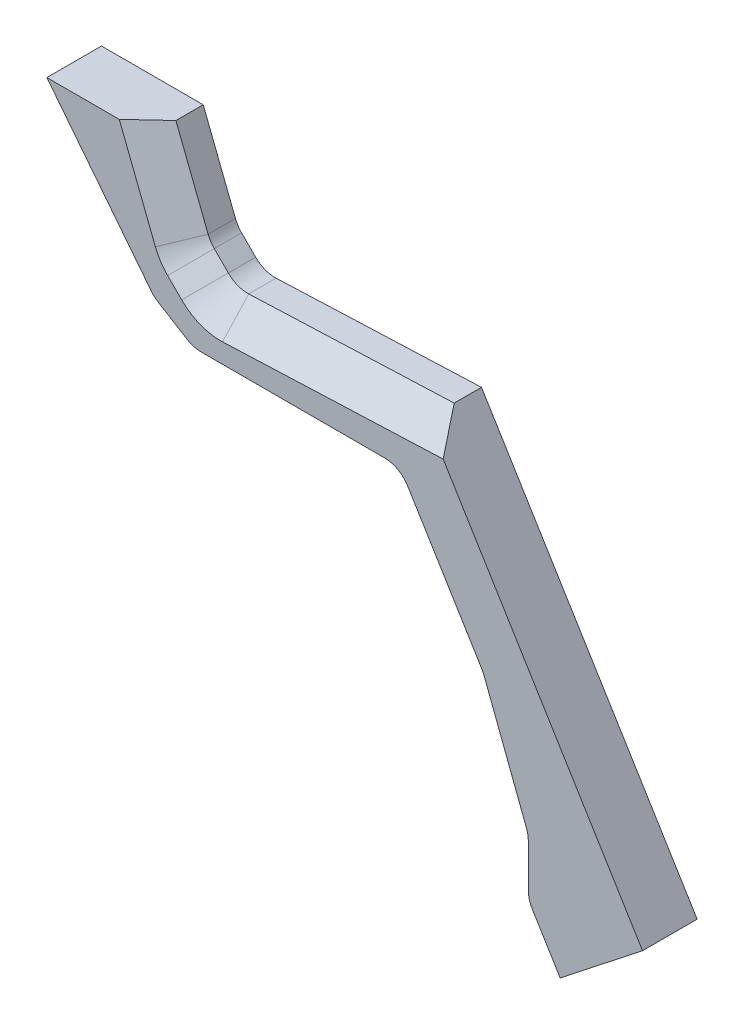
SolidWorks part; units mm, degrees
ref_plane "Front Plane" through (0, 0, 0) normal (0, 0, 1) x (1, 0, 0)
ref_plane "Top Plane" through (0, 0, 0) normal (0, 1, 0) x (1, 0, 0)
ref_plane "Right Plane" through (0, 0, 0) normal (1, 0, 0) x (0, 0, -1)
sketch "Sketch1" plane through (0, 0, 0) normal (0, 0, 1) x (1, 0, 0)
  line L0 (536.696, 136.2549) -> (560.9431, 105.4362)
  line L1 (536.696, 136.2549) -> (607.9061, 136.2549) construction
  line L2 (572.5936, 98.9345) -> (615.1948, 98.9345)
  line L3 (620.6127, 95.8964) -> (637.801, 67.7789)
  line L4 (638.3138, 66.7361) -> (648.2078, 40.8769)
  line L5 (648.6271, 38.6077) -> (648.6271, 28.5432)
  line L6 (649.5592, 25.2312) -> (652.3824, 20.6128)
  line L7 (652.3824, 20.6128) -> (656.0389, 14.6314)
  line L8 (656.0389, 14.6314) -> (675.1811, 29.6919)
  line L9 (675.1811, 29.6919) -> (625.0443, 111.7085)
  line L10 (625.0443, 111.7085) -> (577.2803, 109.8048)
  line L11 (567.8459, 117.1036) -> (560.3494, 136.2549)
  line L12 (536.696, 136.2549) -> (560.3494, 136.2549)
  line L13 (562.6176, 103.9472) -> (569.2776, 99.8691)
  line L14 (569.2689, 114.9281) -> (572.5373, 111.6597)
  arc A0 (648.6271, 28.5432) -> (649.5592, 25.2312) centre (654.9771, 28.5432) ccw
  arc A1 (615.1948, 98.9345) -> (620.6127, 95.8964) centre (615.1948, 92.5845) cw
  arc A2 (637.801, 67.7789) -> (638.3138, 66.7361) centre (632.3831, 64.4669) cw
  arc A3 (648.2078, 40.8769) -> (648.6271, 38.6077) centre (642.2771, 38.6077) cw
  arc A4 (569.2776, 99.8691) -> (572.5936, 98.9345) centre (572.5936, 105.2845) ccw
  arc A5 (562.6176, 103.9472) -> (560.9431, 105.4362) centre (565.9337, 109.3626) cw
  arc A6 (572.5373, 111.6597) -> (577.2803, 109.8048) centre (577.0274, 116.1498) ccw
  arc A7 (569.2689, 114.9281) -> (567.8459, 117.1036) centre (573.759, 119.4182) cw
  dimension "D1" = 6.35
  dimension "D2" = 6.35
extrude "Boss-Extrude1" add sketch "Sketch1" along normal blind 6.35 and the other way blind 6.35 contours L9 L10 A6 L14 A7 L11 L12 L0 A5 L13 A4 L2 A1 L3 A2 L4 A3 L5 A0 L6 L7 L8
chamfer "Chamfer1" distance 6.35 angle 45 5 edges at (564.0976, 126.6793, 6.35) (568.4449, 115.9423, 6.35) (570.9031, 113.2939, 6.35) (574.7147, 110.2359, 6.35) (601.1623, 110.7567, 6.35)
